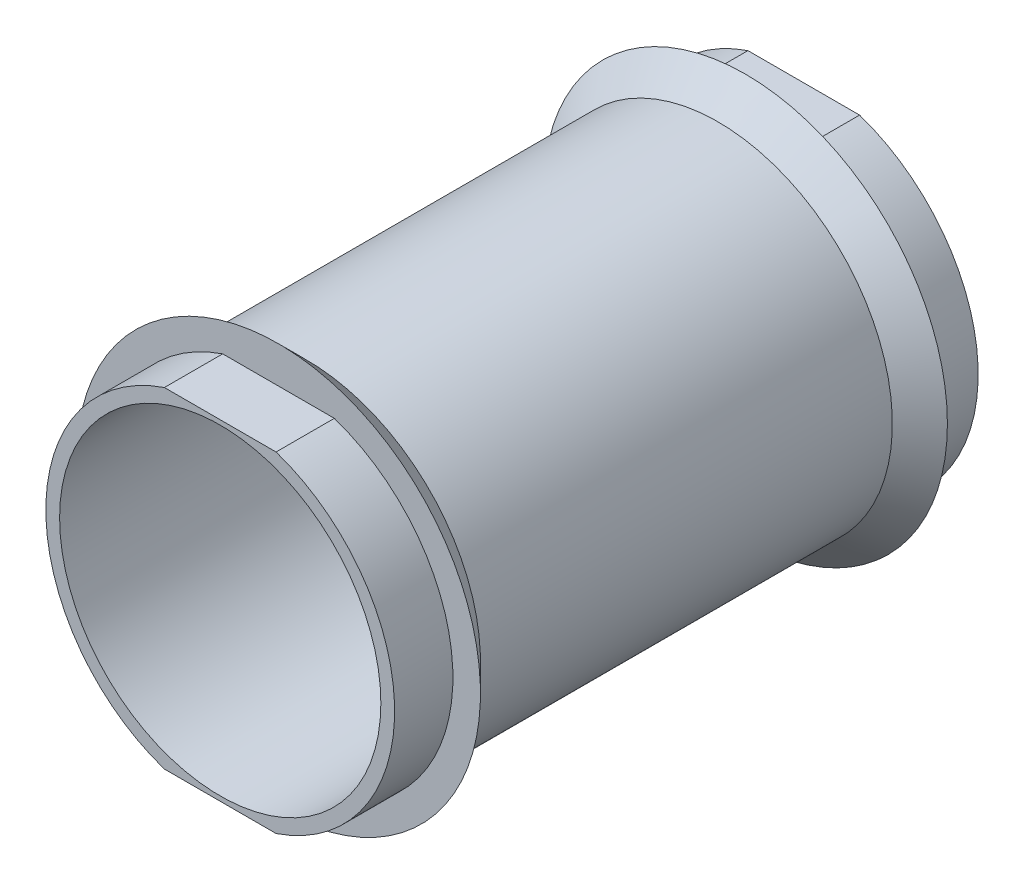
SolidWorks part; units mm, degrees
material "6061-T6 (SS)"
ref_plane "Front Plane" through (0, 0, 0) normal (0, 0, 1) x (1, 0, 0)
ref_plane "Top Plane" through (0, 0, 0) normal (0, 1, 0) x (1, 0, 0)
ref_plane "Right Plane" through (0, 0, 0) normal (1, 0, 0) x (0, 0, -1)
sketch "Sketch1" plane through (0, 0, 0) normal (0, 0, 1) x (1, 0, 0)
  circle A0 centre (0, 0) radius 25.4
  circle A1 centre (0, 0) radius 12.7
  dimension "D1" = 50.8
  dimension "D2" = 12.7
extrude "Stock Dimensions" add sketch "Sketch1" along normal mid plane 63.575
sketch "Sketch2" plane through (0, 0, 31.7875) normal (0, 0, 1) x (1, 0, 0)
  circle A0 centre (0, 0) radius 22
  dimension "Drum OD" = 44
extrude "Outer Diameter" cut sketch "Sketch2" against normal through all flip side to cut
sketch "Sketch3" plane through (0, 0, 31.7875) normal (0, 0, 1) x (1, 0, 0)
  circle A0 centre (0, 0) radius 17.5 construction
  circle A1 centre (0, 0) radius 17.5
extrude "Rotor Seat" cut sketch "Sketch3" against normal up to surface (25 mm away)
sketch "Sketch4" plane through (0, 0, 6.7875) normal (0, 0, 1) x (1, 0, 0)
  circle A0 centre (0, 0) radius 15 construction
  circle A1 centre (0, 0) radius 15
extrude "Inner Bearing Seat" cut sketch "Sketch4" against normal up to surface (10 mm away)
sketch "Sketch5" plane through (0, 0, -31.7875) normal (0, 0, -1) x (-1, 0, 0)
  circle A0 centre (0, 0) radius 15 construction
  circle A1 centre (0, 0) radius 15
extrude "Outer Bearing Seat" cut sketch "Sketch5" against normal up to surface (9 mm away)
sketch "Sketch6" plane through (0, 0, 31.7875) normal (0, 0, 1) x (1, 0, 0)
  line L0 (-17.9209, 18) -> (17.9209, 18)
  circle A0 centre (0, 0) radius 22 construction
  circle A1 centre (0, 0) radius 17.5 construction
  circle A2 centre (0, 0) radius 22 construction
  circle A3 centre (0, 0) radius 17.5 construction
  circle A4 centre (0, 0) radius 25.4 construction
  circle A5 centre (0, 0) radius 25.4 construction
  arc A6 (-17.9209, 18) -> (17.9209, 18) centre (0, 0) cw
  point P5 (0, 17.5)
  dimension "D1" = 0.5
extrude "Indexing Cut" cut sketch "Sketch6" against normal blind 6.35
mirror "Indexing Horizontal Mirror" about plane through (0, 0, 0) normal (0, 0, 1) of "Indexing Cut"
mirror "Indexing Vertical Mirror" about plane through (0, 0, 0) normal (0, 1, 0) of "Indexing Horizontal Mirror"
sketch "Sketch7" plane through (0, 0, 0) normal (0, 1, 0) x (1, 0, 0)
  line L0 (-12.6491, -25.4375) -> (12.6491, -25.4375) construction
  line L1 (-12.6491, -25.4375) -> (12.6491, -25.4375) construction
  line L2 (12.6491, 25.4375) -> (-12.6491, 25.4375) construction
  line L3 (12.6491, 25.4375) -> (-12.6491, 25.4375) construction
  line L4 (-22, 31.7875) -> (-22, -31.7875)
  line L5 (22, -31.7875) -> (22, 31.7875)
  line L6 (22, -31.7875) -> (22, 31.7875) construction
  line L7 (-22, 31.7875) -> (-22, -31.7875) construction
  line L8 (-12.6491, 25.4375) -> (-22, 25.4375) construction
  line L9 (-12.6491, -25.4375) -> (-22, -25.4375) construction
  line L10 (-22, -25.4375) -> (-19, -22.4375)
  line L11 (-19, -22.4375) -> (-19, 22.4375)
  line L12 (-19, 22.4375) -> (-22, 25.4375)
  line L13 (0, 21.7122) -> (0, -3.7035) construction
  line L14 (-22, 25.4375) -> (-22, -25.4375)
  dimension "D1" = 38
  dimension "D2" = 45
revolve "Weight Removal" cut sketch "Sketch7" angle 360 about L13
sketch "Sketch8" plane through (0, 0, 31.7875) normal (0, 0, 1) x (1, 0, 0)
  circle A0 centre (0, 0) radius 19 construction
  circle A1 centre (0, 0) radius 19
extrude "Cut-Extrude7" cut sketch "Sketch8" against normal up to surface (6.35 mm away) flip side to cut up to face at (0, 20, 25.4375)
sketch "Sketch9" plane through (0, 0, -31.7875) normal (0, 0, -1) x (-1, 0, 0)
  line L2 (6.0828, 18) -> (-6.0828, 18)
  line L3 (-6.0828, -18) -> (6.0828, -18)
  line L4 (6.0828, 18) -> (-6.0828, 18)
  line L5 (-6.0828, -18) -> (6.0828, -18)
  arc A3 (6.0828, -18) -> (6.0828, 18) centre (0, 0) ccw
  arc A4 (-6.0828, 18) -> (-6.0828, -18) centre (0, 0) ccw
  arc A5 (6.0828, -18) -> (6.0828, 18) centre (0, 0) ccw
  arc A6 (-6.0828, 18) -> (-6.0828, -18) centre (0, 0) ccw
  dimension "D1" = 0
extrude "Cut-Extrude8" cut sketch "Sketch9" against normal up to surface (6.35 mm away) flip side to cut up to face at (0, 20, -25.4375)
sketch "Sketch10" plane through (0, 0, -3.2125) normal (0, 0, 1) x (1, 0, 0)
  circle A0 centre (0, 0) radius 13
  circle A1 centre (0, 0) radius 15 construction
  dimension "D1" = 2
extrude "Inner Bore" cut sketch "Sketch10" against normal through all
